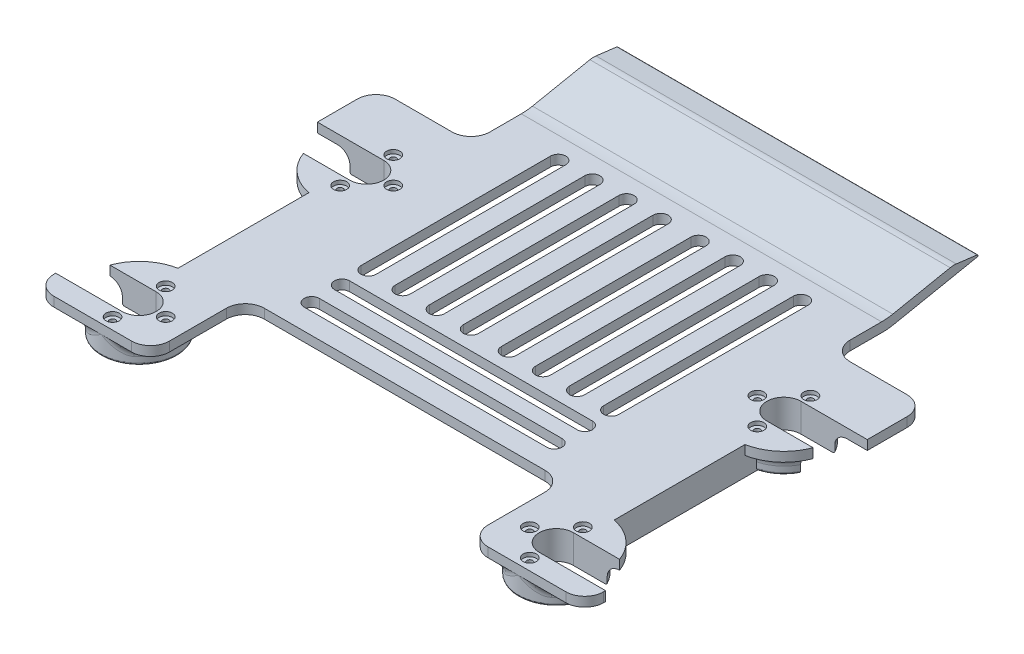
SolidWorks part; units mm, degrees
ref_plane "前视基准面" through (0, 0, 0) normal (0, 0, 1) x (1, 0, 0)
ref_plane "上视基准面" through (0, 0, 0) normal (0, 1, 0) x (1, 0, 0)
ref_plane "右视基准面" through (0, 0, 0) normal (1, 0, 0) x (0, 0, -1)
sketch "Sketch2" plane through (0, 0, 0) normal (1, 0, 0) x (0, 0, -1)
  line L0 (0, 0) -> (0, -5)
  line L1 (0, -5) -> (157.0294, -5)
  line L2 (162.9129, -4.4174) -> (210, 5)
  line L3 (210, 5) -> (209.0194, 9.9029)
  line L4 (209.0194, 9.9029) -> (162.4178, 0.5826)
  line L5 (0, 0) -> (156.5343, 0)
  arc A0 (157.0294, -5) -> (162.9129, -4.4174) centre (157.0294, 25) ccw
  arc A1 (156.5343, 0) -> (162.4178, 0.5826) centre (156.5343, 30) ccw
  point P11 (160, -5)
  dimension "D6" = 30
  dimension "D1" = 5
  dimension "D2" = 5
  dimension "D3" = 160
  dimension "D4" = 210
  dimension "D5" = 10
extrude "Boss-Extrude2" add sketch "Sketch2" along normal blind 190
sketch "Sketch3" plane through (0, 0, 0) normal (0, 1, 0) x (1, 0, 0)
  line L0 (0, 130) -> (-50, 130)
  line L1 (0, 156.5343) -> (0, 0) construction
  line L2 (-50, 130) -> (-50, 0)
  line L3 (-50, 0) -> (0, 0)
  line L4 (0, 0) -> (0, 130)
  line L5 (95, 0) -> (95, 71.7642) construction
  line L6 (190, 0) -> (0, 0) construction
  line L7 (240, 0) -> (190, 0)
  line L8 (240, 130) -> (240, 0)
  line L9 (190, 130) -> (240, 130)
  line L10 (190, 0) -> (190, 130)
  dimension "D1" = 130
  dimension "D2" = 50
extrude "Boss-Extrude3" add sketch "Sketch3" against normal blind 5
sketch "Sketch14" plane through (0, -5, 0) normal (0, -1, 0) x (1, 0, 0)
  line L0 (-50, 0) -> (-50, 50)
  line L1 (-50, 50) -> (11, 50)
  line L2 (11, 50) -> (11, 0)
  line L3 (240, 0) -> (-50, 0) construction
  line L4 (11, 0) -> (-50, 0)
  line L5 (95, 0) -> (95, -23.7201) construction
  line L6 (179, 50) -> (179, 0)
  line L7 (240, 50) -> (179, 50)
  line L8 (240, 0) -> (240, 50)
  line L9 (179, 0) -> (240, 0)
  dimension "D1" = 50
  dimension "D2" = 61
extrude "Boss-Extrude6" add sketch "Sketch14" against normal blind 5
fillet "Fillet1" radius 10 4 edges at (240, -2.5, -130) (190, -2.5, -130) (0, -2.5, -130) (-50, -2.5, -130)
sketch "Sketch5" plane through (0, 0, 0) normal (-1, 0, 0) x (0, 0, 1)
  line L0 (-210, 5) -> (-194.3107, 6.9612)
  line L1 (-209.0194, 9.9029) -> (-162.4178, 0.5826) construction
  line L2 (-194.3107, 6.9612) -> (-209.0194, 9.9029)
  line L3 (-209.0194, 9.9029) -> (-210, 5)
  dimension "D1" = 15
extrude "Cut-Extrude1" cut sketch "Sketch5" against normal through all
fillet "Fillet2" radius 0.5 1 edges at (95, 5, -210)
fillet "Fillet3" radius 10 1 edges at (95, 6.9612, -194.3107)
sketch "Sketch6" plane through (0, 0, 0) normal (0, 1, 0) x (1, 0, 0)
  line L0 (-72.7307, 90) -> (271.6225, 90) construction
  line L1 (179, 0) -> (11, 0) construction
  line L2 (-15, 92.2725) -> (-15, -17.4598) construction
  line L3 (-50, 120) -> (-50, -50) construction
  line L4 (95, 0) -> (95, 66.4141) construction
  line L5 (-58.8862, 30) -> (260.9557, 30) construction
  circle A12 centre (205, -30) radius 20
  circle A13 centre (-15, 90) radius 20
  circle A14 centre (205, 90) radius 20
  circle A15 centre (-15, -30) radius 20
  dimension "D3" = 40
  dimension "D4" = 60
  dimension "D1" = 90
  dimension "D2" = 35
extrude "Boss-Extrude5" add sketch "Sketch6" against normal blind 15
fillet "Fillet4" radius 6 4 edges at (205, -5, -70) (-15, -5, -70) (-15, -5, 50) (205, -5, 50)
sketch "Sketch10" plane through (0, -15, 0) normal (0, -1, 0) x (1, 0, 0)
  line L0 (-15, 30) -> (-15, -90) construction
  line L1 (-73.8826, -90) -> (27.4498, -90) construction
  line L2 (95, 0) -> (95, -90.2367) construction
  line L3 (179, 0) -> (11, 0) construction
  line L4 (263.8826, -90) -> (162.5502, -90) construction
  line L5 (205, 30) -> (205, -90) construction
  line L6 (-15, -30) -> (47.4183, -30) construction
  line L7 (263.8826, 30) -> (162.5502, 30) construction
  line L8 (-73.8826, 30) -> (27.4498, 30) construction
  circle A0 centre (-15, -90) radius 14 construction
  circle A1 centre (-15, -76) radius 1.6
  circle A2 centre (-1, -90) radius 1.6
  circle A3 centre (-15, -104) radius 1.6
  circle A4 centre (-29, -90) radius 1.6
  circle A5 centre (-15, -90) radius 9
  circle A6 centre (205, -90) radius 14 construction
  circle A7 centre (205, -90) radius 9
  circle A8 centre (219, -90) radius 1.6
  circle A9 centre (205, -104) radius 1.6
  circle A10 centre (191, -90) radius 1.6
  circle A11 centre (205, -76) radius 1.6
  circle A12 centre (205, 30) radius 14 construction
  circle A13 centre (-15, 30) radius 14 construction
  circle A14 centre (205, 16) radius 1.6
  circle A15 centre (191, 30) radius 1.6
  circle A16 centre (205, 44) radius 1.6
  circle A17 centre (219, 30) radius 1.6
  circle A18 centre (205, 30) radius 9
  circle A19 centre (-15, 30) radius 9
  circle A20 centre (-29, 30) radius 1.6
  circle A21 centre (-15, 44) radius 1.6
  circle A22 centre (-1, 30) radius 1.6
  circle A23 centre (-15, 16) radius 1.6
  point P18 (-15, -90)
  point P36 (205, -90)
  point P63 (205, 30)
  point P64 (-15, 30)
  dimension "D1" = 28
  dimension "D2" = 3.2
  dimension "D4" = 18
  dimension "D3" = 4
extrude "Cut-Extrude5" cut sketch "Sketch10" against normal through all
sketch "Sketch11" plane through (0, 0, 0) normal (0, 1, 0) x (1, 0, 0)
  line L0 (-15, 99) -> (-15, 81)
  line L1 (-15, 81) -> (-50, 81)
  line L2 (-50, 120) -> (-50, -50) construction
  line L3 (-50, 81) -> (-50, 99)
  line L4 (-50, 99) -> (-15, 99)
  line L5 (95, 0) -> (95, 44.1762) construction
  line L6 (179, 0) -> (11, 0) construction
  line L7 (240, 81) -> (240, 99)
  line L8 (205, 81) -> (240, 81)
  line L9 (205, 99) -> (205, 81)
  line L10 (240, 99) -> (205, 99)
  line L11 (-1, 90) -> (-1, -30) construction
  line L12 (-1, 30) -> (42.0763, 30) construction
  line L13 (205, -21) -> (240, -21)
  line L14 (205, -39) -> (205, -21)
  line L15 (240, -39) -> (205, -39)
  line L16 (240, -21) -> (240, -39)
  line L17 (-50, -21) -> (-50, -39)
  line L18 (-15, -21) -> (-50, -21)
  line L19 (-15, -39) -> (-15, -21)
  line L20 (-50, -39) -> (-15, -39)
  circle A0 centre (-15, 90) radius 9 construction
extrude "Cut-Extrude6" cut sketch "Sketch11" against normal through all
sketch "Sketch12" plane through (0, 0, 0) normal (0, 1, 0) x (1, 0, 0)
  line L0 (95, 0) -> (95, 33.5213) construction
  line L1 (179, 0) -> (11, 0) construction
  line L2 (-15, 90) -> (-15, -30) construction
  line L3 (-15, 30) -> (41.8478, 30) construction
  circle A0 centre (-15, 104) radius 3.5
  circle A1 centre (-1, 90) radius 3.5
  circle A2 centre (-15, 76) radius 3.5
  circle A3 centre (205, 76) radius 3.5
  circle A4 centre (191, 90) radius 3.5
  circle A5 centre (205, 104) radius 3.5
  circle A6 centre (205, -44) radius 3.5
  circle A7 centre (191, -30) radius 3.5
  circle A8 centre (205, -16) radius 3.5
  circle A9 centre (-15, -16) radius 3.5
  circle A10 centre (-1, -30) radius 3.5
  circle A11 centre (-15, -44) radius 3.5
  dimension "D1" = 7
  dimension "D2" = 7
  dimension "D3" = 7
extrude "Cut-Extrude7" cut sketch "Sketch12" against normal blind 2
fillet "Fillet5" radius 1 4 edges at (185, -15, -90) (5, -15, -90) (185, -15, 30) (5, -15, 30) tangent propagation no
fillet "Fillet6" radius 10 6 edges at (179, -2.5, 0) (11, -2.5, 0) (240, -2.5, 50) (179, -2.5, 50) (-50, -2.5, 50) (11, -2.5, 50)
sketch "Sketch15" plane through (0, -5, 0) normal (0, -1, 0) x (1, 0, 0)
  line L0 (-15, 16) -> (-15, -76) construction
  line L1 (95, 0) -> (95, -40.8615) construction
  line L2 (169, 0) -> (21, 0) construction
  line L3 (-20, 13) -> (-20, -73)
  line L4 (-10, 13) -> (-10, -73)
  line L5 (-20, 13) -> (-10, 13)
  line L6 (-20, -73) -> (-10, -73)
  line L7 (-20, 16) -> (-20, -76) construction
  line L8 (-10, 16) -> (-10, -76) construction
  line L9 (210, 13) -> (200, 13)
  line L10 (210, 13) -> (210, -73)
  line L11 (210, -73) -> (200, -73)
  line L12 (200, 13) -> (200, -73)
  dimension "D3" = 3
  dimension "D4" = 3
  dimension "D1" = 5
  dimension "D2" = 5
extrude "Boss-Extrude7" add sketch "Sketch15" along normal blind 10
sketch "Sketch16" plane through (0, -5, 0) normal (0, -1, 0) x (1, 0, 0)
  line L0 (229.3926, 21) -> (240, 21)
  line L1 (240, 21) -> (240, -81)
  line L2 (240, -81) -> (229.3926, -81)
  line L3 (210, 4.4853) -> (210, -64.4853)
  line L4 (95, 0) -> (95, -61.8626) construction
  line L5 (169, 0) -> (21, 0) construction
  line L6 (-50, -81) -> (-39.3926, -81)
  line L7 (-50, 21) -> (-50, -81)
  line L8 (-39.3926, 21) -> (-50, 21)
  line L9 (-20, 4.4853) -> (-20, -64.4853)
  arc A0 (210, 4.4853) -> (229.3926, 21) centre (205, 30) ccw
  arc A1 (229.3926, -81) -> (210, -64.4853) centre (205, -90) ccw
  arc A2 (-20, 4.4853) -> (-39.3926, 21) centre (-15, 30) cw
  arc A3 (-39.3926, -81) -> (-20, -64.4853) centre (-15, -90) cw
extrude "Cut-Extrude8" cut sketch "Sketch16" against normal through all
sketch "Sketch17" plane through (0, -5, 0) normal (0, -1, 0) x (1, 0, 0)
  line L0 (95, 0) -> (95, -199.0372) construction
  line L1 (169, 0) -> (21, 0) construction
  line L2 (85, -45) -> (85, -145) construction
  line L3 (89, -45) -> (89, -145)
  line L4 (81, -45) -> (81, -145)
  line L5 (67, -45) -> (67, -145) construction
  line L6 (71, -45) -> (71, -145)
  line L7 (63, -45) -> (63, -145)
  line L8 (49, -45) -> (49, -145) construction
  line L9 (53, -45) -> (53, -145)
  line L10 (45, -45) -> (45, -145)
  line L11 (31, -45) -> (31, -145) construction
  line L12 (35, -45) -> (35, -145)
  line L13 (27, -45) -> (27, -145)
  line L14 (159, -45) -> (159, -145) construction
  line L15 (155, -45) -> (155, -145)
  line L16 (163, -45) -> (163, -145)
  line L17 (141, -45) -> (141, -145) construction
  line L18 (137, -45) -> (137, -145)
  line L19 (145, -45) -> (145, -145)
  line L20 (123, -45) -> (123, -145) construction
  line L21 (119, -45) -> (119, -145)
  line L22 (127, -45) -> (127, -145)
  line L23 (105, -45) -> (105, -145) construction
  line L24 (101, -45) -> (101, -145)
  line L25 (109, -45) -> (109, -145)
  arc A0 (89, -45) -> (81, -45) centre (85, -45) ccw
  arc A1 (81, -145) -> (89, -145) centre (85, -145) ccw
  arc A2 (71, -45) -> (63, -45) centre (67, -45) ccw
  arc A3 (63, -145) -> (71, -145) centre (67, -145) ccw
  arc A4 (53, -45) -> (45, -45) centre (49, -45) ccw
  arc A5 (45, -145) -> (53, -145) centre (49, -145) ccw
  arc A6 (35, -45) -> (27, -45) centre (31, -45) ccw
  arc A7 (27, -145) -> (35, -145) centre (31, -145) ccw
  arc A8 (155, -45) -> (163, -45) centre (159, -45) cw
  arc A9 (163, -145) -> (155, -145) centre (159, -145) cw
  arc A10 (137, -45) -> (145, -45) centre (141, -45) cw
  arc A11 (145, -145) -> (137, -145) centre (141, -145) cw
  arc A12 (119, -45) -> (127, -45) centre (123, -45) cw
  arc A13 (127, -145) -> (119, -145) centre (123, -145) cw
  arc A14 (101, -45) -> (109, -45) centre (105, -45) cw
  arc A15 (109, -145) -> (101, -145) centre (105, -145) cw
  point P6 (85, -95)
  point P14 (67, -95)
  point P21 (49, -95)
  point P28 (31, -95)
  point P34 (159, -95)
  point P41 (141, -95)
  point P48 (123, -95)
  point P55 (105, -95)
  dimension "D3" = 4
  dimension "D1" = 45
  dimension "D2" = 100
  dimension "D4" = 10
  dimension "D6" = 54
  dimension "D5" = 4
extrude "Cut-Extrude9" cut sketch "Sketch17" against normal through all
sketch "Sketch18" plane through (0, -5, 0) normal (0, -1, 0) x (1, 0, 0)
  line L0 (31, -45) -> (31, 10.3223) construction
  line L1 (159, -45) -> (159, 10.3223) construction
  line L2 (31, -31) -> (159, -31) construction
  line L3 (31, -27) -> (159, -27)
  line L4 (31, -35) -> (159, -35)
  line L5 (31, -15) -> (159, -15) construction
  line L6 (31, -11) -> (159, -11)
  line L7 (31, -19) -> (159, -19)
  arc A0 (31, -27) -> (31, -35) centre (31, -31) ccw
  arc A1 (159, -35) -> (159, -27) centre (159, -31) ccw
  arc A2 (31, -11) -> (31, -19) centre (31, -15) ccw
  arc A3 (159, -19) -> (159, -11) centre (159, -15) ccw
  point P8 (95, -31)
  point P16 (95, -15)
  dimension "D2" = 4
  dimension "D1" = 14
  dimension "D4" = 16
  dimension "D3" = 2
extrude "Cut-Extrude10" cut sketch "Sketch18" against normal through all
